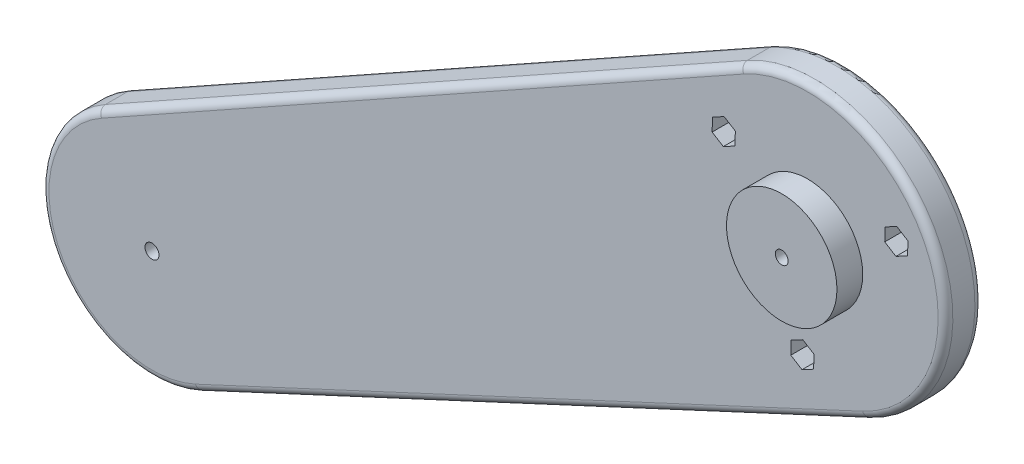
SolidWorks part; units mm, degrees
ref_plane "Front Plane" through (0, 0, 0) normal (0, 0, 1) x (1, 0, 0)
ref_plane "Top Plane" through (0, 0, 0) normal (0, 1, 0) x (1, 0, 0)
ref_plane "Right Plane" through (0, 0, 0) normal (1, 0, 0) x (0, 0, -1)
sketch "Sketch1" plane through (0, 0, 0) normal (0, 0, 1) x (1, 0, 0)
  line L3 (-192.7236, -64.8661) -> (-18.3113, 32.7253)
  line L4 (-165.4289, -118.2509) -> (15.8071, -34.0057)
  arc A0 (15.8071, -34.0057) -> (-18.3113, 32.7253) centre (0, 0) ccw
  arc A1 (-192.7236, -64.8661) -> (-165.4289, -118.2509) centre (-178.0746, -91.0463) ccw
  dimension "D1" = 75
  dimension "D2" = 60
  dimension "D3" = 200
extrude "Boss-Extrude1" add sketch "Sketch1" along normal blind 10
sketch "Sketch3" plane through (0, 0, 10) normal (0, 0, 1) x (1, 0, 0)
  line L2 (-4.4241, -25.1889) -> (-4.5358, -28.7672)
  line L3 (27.2927, 14.0337) -> (24.2497, 15.9196)
  line L4 (24.2497, 15.9196) -> (21.095, 14.2272)
  line L5 (21.095, 14.2272) -> (20.9833, 10.6489)
  line L6 (20.9833, 10.6489) -> (24.0263, 8.7631)
  line L7 (24.0263, 8.7631) -> (27.181, 10.4555)
  line L8 (27.181, 10.4555) -> (27.2927, 14.0337)
  line L9 (-4.5358, -28.7672) -> (-1.4928, -30.6531)
  line L10 (-1.4928, -30.6531) -> (1.6619, -28.9607)
  line L11 (1.6619, -28.9607) -> (1.7736, -25.3824)
  line L12 (1.7736, -25.3824) -> (-1.2694, -23.4965)
  line L13 (-1.2694, -23.4965) -> (-4.4241, -25.1889)
  line L14 (-19.6022, 16.4259) -> (-22.6452, 18.3117)
  line L15 (-22.6452, 18.3117) -> (-25.7999, 16.6193)
  line L16 (-25.7999, 16.6193) -> (-25.9116, 13.0411)
  line L17 (-25.9116, 13.0411) -> (-22.8686, 11.1552)
  line L18 (-22.8686, 11.1552) -> (-19.7139, 12.8476)
  line L19 (-19.7139, 12.8476) -> (-19.6022, 16.4259)
  circle A1 centre (24.138, 12.3413) radius 3.1004 construction
  point P28 (0, 0)
  dimension "D2" = 3.58
  dimension "D3" = 3
fillet "Fillet1" radius 2 8 edges at (33.389, 17.0712, 10) (-74.8109, -76.1283, 10) (-204.7858, -104.7033, 10) (-105.5174, -16.0704, 10) (-74.8109, -76.1283, 0) (33.389, 17.0712, 0) (-105.5174, -16.0704, 0) (-204.7858, -104.7033, 0)
ref_plane "Plane1" through (0, 0, 5) normal (0, 0, 1) x (1, 0, 0)
extrude "Cut-Extrude8" cut sketch "Sketch3" against normal blind 5
sketch "Sketch10" plane through (0, 0, 5) normal (0, 0, 1) x (1, 0, 0)
  circle A1 centre (24.0401, 12.2913) radius 1.75
  dimension "D1" = 3.5
extrude "Cut-Extrude9" cut sketch "Sketch10" against normal blind 70 and the other way blind 1 contours A1 | A1 region at (24.0401, 12.2913, 5)
pattern_circular "CirPattern1" count 3 over 360 about axis through (0, 0, 10) along (0, 0, -1) of "Cut-Extrude9" reverse direction yes
sketch "Sketch12" plane through (0, 0, 10) normal (0, 0, 1) x (1, 0, 0)
  circle A5 centre (0, 0) radius 15
  dimension "D1" = 30
extrude "Boss-Extrude2" add sketch "Sketch12" along normal blind 7
sketch "Sketch14" plane through (0, 0, 0) normal (0, 0, -1) x (-1, 0, 0)
  line L0 (0, 0) -> (178.0746, -91.0463)
  line L2 (181.6546, -91.0463) -> (179.8646, -87.946)
  line L3 (179.8646, -87.946) -> (176.2846, -87.946)
  line L4 (176.2846, -87.946) -> (174.4946, -91.0463)
  line L5 (174.4946, -91.0463) -> (176.2846, -94.1467)
  line L6 (176.2846, -94.1467) -> (179.8646, -94.1467)
  line L7 (179.8646, -94.1467) -> (181.6546, -91.0463)
  circle A0 centre (178.0746, -91.0463) radius 3.1004 construction
  dimension "D1" = 3.58
extrude "Cut-Extrude11" cut sketch "Sketch14" against normal blind 5 contours L6 L7 L2 L3 L4 L5 region at (-180.6776, -92.5492, 0)
sketch "Sketch15" plane through (0, 0, 5) normal (0, 0, -1) x (-1, 0, 0)
  circle A0 centre (178.0746, -91.0463) radius 1.9
  dimension "D1" = 3.8
extrude "Cut-Extrude12" cut sketch "Sketch15" against normal blind 5
sketch "Sketch16" plane through (0, 0, 0) normal (0, 0, -1) x (-1, 0, 0)
  circle A0 centre (0, 0) radius 1.75
  dimension "D1" = 3.5
extrude "Cut-Extrude13" cut sketch "Sketch16" against normal blind 18
